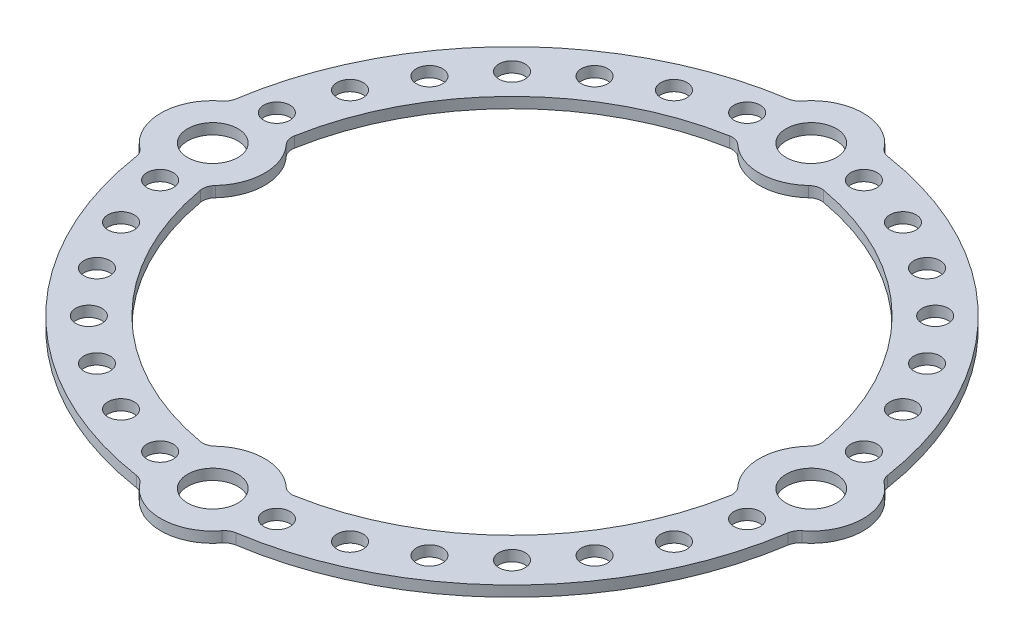
SolidWorks part; units mm, degrees
material "Custom Plastic"
ref_plane "Front Plane" through (0, 0, 0) normal (0, 0, 1) x (1, 0, 0)
ref_plane "Top Plane" through (0, 0, 0) normal (0, 1, 0) x (1, 0, 0)
ref_plane "Right Plane" through (0, 0, 0) normal (1, 0, 0) x (0, 0, -1)
sketch "Sketch1" plane through (0, 0, 0) normal (0, 1, 0) x (1, 0, 0)
  line L0 (0, 44.475) -> (0, -44.475) construction
  line L1 (0, 40.75) -> (0, -40.75) construction
  line L2 (0, 49) -> (0, 39.95) construction
  line L3 (-44.475, 0) -> (44.475, 0) construction
  circle A0 centre (0, 0) radius 39.95
  circle A1 centre (0, 0) radius 49
  circle A2 centre (0, 44.475) radius 3.725
  circle A3 centre (44.475, 0) radius 3.725
  circle A4 centre (0, -44.475) radius 3.725
  circle A5 centre (-44.475, 0) radius 3.725
extrude "Boss-Extrude1" add sketch "Sketch1" along normal blind 1.5875
sketch "Sketch2" plane through (0, 1.5875, 0) normal (0, 1, 0) x (1, 0, 0)
  circle A0 centre (-44.475, 0) radius 7.725
  circle A1 centre (-44.475, 0) radius 3.725 construction
  circle A3 centre (-44.475, 0) radius 3.725
  dimension "D1" = 4
extrude "Boss-Extrude3" add sketch "Sketch2" against normal up to surface (1.5875 mm away) up to face at (0, 0, 48.2)
fillet "Fillet1" radius 2 4 edges at (-39.5093, 0.7937, -5.9176) (-39.5093, 0.7937, 5.9176) (-48.5593, 0.7937, 6.557) (-48.5593, 0.7937, -6.557)
ref_axis "Axis1" through (0, 0, 0) along (0, 1, 0)
pattern_circular "CirPattern1" count 4 every 90 about axis through (0, 0, 0) along (0, 1, 0) of "Boss-Extrude3", "Fillet1"
sketch "Sketch4" plane through (0, 1.5875, 0) normal (0, 1, 0) x (1, 0, 0)
  line L1 (-44.475, 0) -> (-31.4486, -31.4486) construction
  line L2 (-31.4486, -31.4486) -> (0, -44.475) construction
  line L3 (0, -44.475) -> (31.4486, -31.4486) construction
  line L4 (31.4486, -31.4486) -> (44.475, 0) construction
  line L5 (44.475, 0) -> (31.4486, 31.4486) construction
  line L6 (31.4486, 31.4486) -> (0, 44.475) construction
  line L7 (0, 44.475) -> (-31.4486, 31.4486) construction
  line L8 (-31.4486, 31.4486) -> (-44.475, 0) construction
  circle A0 centre (-31.4486, 31.4486) radius 1.95
  circle A1 centre (0, 0) radius 41.0895 construction
extrude "Cut-Extrude3" cut sketch "Sketch4" against normal up to surface (1.5875 mm away) contours A0 up to face at (0, 0, 0)
pattern_circular "CirPattern2" count 32 over 360 about axis through (0, 0, 0) along (0, 1, 0) of "Cut-Extrude3"
